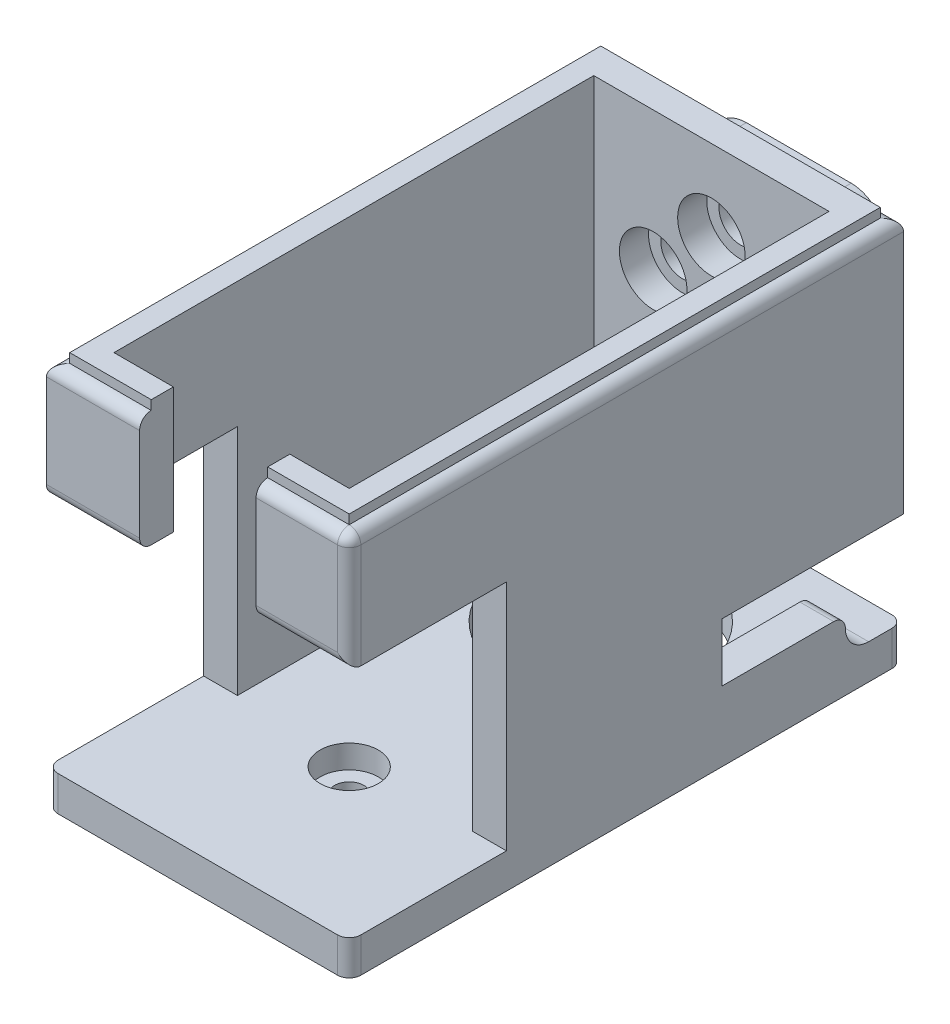
SolidWorks part; units mm, degrees
other "Markup1"
sketch "Sketch34" plane through (-13, 10, 23.5) normal (-0.1734, 0.635, 0.7528) x (0.9767, 0.2093, 0.0485)
ref_plane "Front Plane" through (0, 0, 0) normal (0, 0, 1) x (1, 0, 0)
ref_plane "Top Plane" through (0, 0, 0) normal (0, 1, 0) x (1, 0, 0)
ref_plane "Right Plane" through (0, 0, 0) normal (1, 0, 0) x (0, 0, -1)
sketch "Sketch1" plane through (0, 0, 0) normal (0, 1, 0) x (1, 0, 0)
  line L0 (5, -23.5) -> (13, -23.5)
  line L1 (-10, 20.5) -> (10, 20.5)
  line L2 (-10, 20.5) -> (-10, -20.5)
  line L3 (-10, -20.5) -> (-5, -20.5)
  line L4 (10, 20.5) -> (10, -20.5)
  line L5 (-10, 20.5) -> (10, -20.5) construction
  line L6 (-10, -20.5) -> (10, 20.5) construction
  line L7 (-13, 23.5) -> (13, 23.5)
  line L8 (-13, 23.5) -> (-13, -23.5)
  line L9 (-13, -23.5) -> (-5, -23.5)
  line L10 (13, 23.5) -> (13, -23.5)
  line L11 (-13, 23.5) -> (13, -23.5) construction
  line L12 (-13, -23.5) -> (13, 23.5) construction
  line L14 (-5, -20.5) -> (-5, -23.5)
  line L16 (5, -20.5) -> (5, -23.5)
  line L17 (5, -20.5) -> (10, -20.5)
  point P0 (0, 0)
  point P6 (0, 0)
  dimension "D1" = 20
  dimension "D2" = 41
  dimension "D3" = 3
  dimension "D4" = 3
  dimension "D5" = 5
  dimension "D6" = 5
extrude "Boss-Extrude1" add sketch "Sketch1" along normal blind 10
sketch "Sketch2" plane through (13, 0, 0) normal (1, 0, 0) x (0, 0, -1)
  line L0 (-23.5, 0) -> (23.5, 0) construction
  line L1 (-10, 0) -> (10, 0)
  line L2 (-10, 0) -> (-10, -17)
  line L3 (-10, -17) -> (10, -17)
  line L4 (10, 0) -> (10, -17)
  dimension "D1" = 10
  dimension "D2" = 10
  dimension "D3" = 17
extrude "Boss-Extrude2" add sketch "Sketch2" against normal blind 3
ref_plane "Plane1" through (0, 0, 0) normal (1, 0, 0) x (0, 0, -1)
mirror "Mirror1" about plane through (0, 0, 0) normal (1, 0, 0) of "Boss-Extrude2"
sketch "Sketch3" plane through (0, -17, 0) normal (0, -1, 0) x (1, 0, 0)
  line L1 (-13, 23.5) -> (13, 23.5)
  line L2 (-13, 23.5) -> (-13, -23.5)
  line L3 (-13, -23.5) -> (13, -23.5)
  line L4 (13, 23.5) -> (13, -23.5)
extrude "Boss-Extrude3" add sketch "Sketch3" along normal blind 3
sketch "Sketch5" plane through (0, -20, 0) normal (0, -1, 0) x (1, 0, 0)
  line L1 (10, 20.5) -> (5, 20.5) construction
  line L2 (10, 10) -> (10, -10) construction
  line L3 (-10, 10) -> (-10, -10) construction
  line L4 (-8, -4.5) -> (8, -4.5)
  line L5 (-8, -4.5) -> (-8, -8.5)
  line L6 (-8, -8.5) -> (8, -8.5)
  line L7 (8, -4.5) -> (8, -8.5)
  line L8 (-8, -12.5) -> (8, -12.5)
  line L9 (-8, -12.5) -> (-8, -16.5)
  line L10 (-8, -16.5) -> (8, -16.5)
  line L11 (8, -12.5) -> (8, -16.5)
  line L12 (-10, -10) -> (-10, -20.5) construction
  line L13 (10, -20.5) -> (10, -10) construction
  line L14 (-10, -20.5) -> (10, -20.5) construction
  circle A0 centre (0, 10.5) radius 8
  dimension "D1" = 10
  dimension "D2" = 10
  dimension "D3" = 2
  dimension "D4" = 2
  dimension "D5" = 2
  dimension "D6" = 2
  dimension "D7" = 4
  dimension "D8" = 4
  dimension "D9" = 4
  dimension "D10" = 4
extrude "Cut-Extrude1" cut sketch "Sketch5" against normal through all
sketch "Sketch6" plane through (13, 0, 0) normal (1, 0, 0) x (0, 0, -1)
  line L0 (23.5, -20) -> (23.5, 20.7) construction
  line L1 (23.5, -20) -> (-23.5422, -20) construction
  line L2 (23.5, -20) -> (23.5, 20.7) construction
  line L3 (23.5, 20.7) -> (-23.5422, 20.7) construction
  line L4 (-23.5422, -20) -> (-23.5422, 20.7) construction
  line L5 (23.5, -20) -> (23.5, 20.7) construction
  line L6 (23.5, 0.35) -> (-23.5422, 0.35) construction
  line L7 (10, -17) -> (10, 0) construction
  line L8 (23.5, 4.35) -> (29.5, 4.35)
  line L9 (23.5, 4.35) -> (23.5, -3.65)
  line L10 (23.5, -3.65) -> (29.5, -3.65)
  line L11 (29.5, 4.35) -> (29.5, -3.65)
  line L12 (23.5, 0) -> (10, 0)
  line L13 (23.5, 0) -> (23.5, -9.3)
  line L14 (23.5, -9.3) -> (10, -9.3)
  line L15 (10, 0) -> (10, -9.3)
  line M19 (10, -17) -> (10, 0)
  line M20 (10, 0) -> (23.5, 0)
  line M21 (23.5, 0) -> (23.5, 10)
  dimension "D1" = 40.7
  dimension "D2" = 4
  dimension "D3" = 4
  dimension "D4" = 6
  dimension "D5" = 5.65
extrude "Boss-Extrude4" add sketch "Sketch6" against normal blind 26 contours L11 L8 L9 L10 M21 | L14 L13 L9 M20 M19 region at (13, 0.35, -26.5) region at (13, -4.65, -16.75)
sketch "Sketch7" plane through (0, 0, 0) normal (0, 1, 0) x (1, 0, 0)
  line L1 (-10, 20.5) -> (10, 20.5)
  line L2 (-10, 20.5) -> (-10, 10)
  line L3 (-10, 10) -> (10, 10)
  line L4 (10, 20.5) -> (10, 10)
extrude "Cut-Extrude2" cut sketch "Sketch7" against normal blind 10
sketch "Sketch9" plane through (0, 4.35, 0) normal (0, 1, 0) x (1, 0, 0)
  line L0 (13, 23.5) -> (-13, 23.5) construction
  line L1 (-13, 29.5) -> (-5, 29.5)
  line L2 (-13, 29.5) -> (-13, 23.5)
  line L3 (-13, 23.5) -> (-5, 23.5)
  line L4 (-5, 29.5) -> (-5, 23.5)
  line L5 (-13, 23.5) -> (13, 23.5) construction
  line L6 (13, 29.5) -> (5, 29.5)
  line L7 (13, 29.5) -> (13, 23.5)
  line L8 (13, 23.5) -> (5, 23.5)
  line L9 (5, 29.5) -> (5, 23.5)
  dimension "D1" = 8
  dimension "D2" = 8
extrude "Cut-Extrude3" cut sketch "Sketch9" against normal blind 10
sketch "Sketch10" plane through (0, 0, -29.5) normal (0, 0, -1) x (-1, 0, 0)
  line L1 (-15, 15) -> (15, 15)
  line L2 (-15, 15) -> (-15, -15)
  line L3 (-15, -15) -> (15, -15)
  line L4 (15, 15) -> (15, -15)
  line L5 (-15, 15) -> (15, -15) construction
  line L6 (-15, -15) -> (15, 15) construction
  point P0 (0, 0)
  dimension "D1" = 30
  dimension "D2" = 30
extrude "Boss-Extrude5" add sketch "Sketch10" along normal blind 3
sketch "Sketch11" plane through (0, 0, -32.5) normal (0, 0, -1) x (-1, 0, 0)
  circle A0 centre (0, 10) radius 1.75
  circle A4 centre (10, 0) radius 1.75
  circle A5 centre (0, -10) radius 1.75
  circle A6 centre (-10, 0) radius 1.75
  point P12 (-1, 1)
  point P13 (0, 0)
  dimension "D1" = 3.5
  dimension "D3" = 0
  dimension "D4" = 4
  dimension "D5" = 10
  dimension "D6" = 10
  dimension "D2" = 10
extrude "Cut-Extrude4" cut sketch "Sketch11" against normal blind 5
sketch "Sketch12" plane through (0, -20, 0) normal (0, -1, 0) x (1, 0, 0)
  line L9 (-13, 23.5) -> (13, 23.5)
  line L10 (-13, 23.5) -> (-13, -23.5)
  line L11 (-13, -23.5) -> (13, -23.5)
  line L12 (13, 23.5) -> (13, -23.5)
  circle A0 centre (0, 10.5) radius 8
extrude "Boss-Extrude6" add sketch "Sketch12" along normal blind 3
sketch "Sketch14" plane through (0, -17, 0) normal (0, 1, 0) x (1, 0, 0)
  line L1 (-13, 23.5) -> (13, 23.5)
  line L2 (-13, 23.5) -> (-13, -23.5)
  line L3 (-13, -23.5) -> (13, -23.5)
  line L4 (13, 23.5) -> (13, -23.5)
  line L5 (-13, 10) -> (-10, 10)
  line L6 (-13, 10) -> (-13, -10)
  line L7 (-13, -10) -> (-10, -10)
  line L8 (-10, 10) -> (-10, -10)
  line L9 (10, -10) -> (13, -10)
  line L10 (10, -10) -> (10, 10)
  line L11 (10, 10) -> (13, 10)
  line L12 (13, -10) -> (13, 10)
  circle M1 centre (0, -10.5) radius 8
  line M2 (8, 4.5) -> (-8, 4.5)
  line M3 (-8, 4.5) -> (-8, 8.5)
  line M4 (-8, 8.5) -> (8, 8.5)
  line M5 (8, 8.5) -> (8, 4.5)
  line M6 (8, 12.5) -> (-8, 12.5)
  line M7 (-8, 12.5) -> (-8, 16.5)
  line M8 (-8, 16.5) -> (8, 16.5)
  line M9 (8, 16.5) -> (8, 12.5)
  line M10 (13, -10) -> (10, -10)
  line M11 (10, -10) -> (10, 10)
  line M12 (10, 10) -> (13, 10)
  line M13 (13, 10) -> (13, 23.5)
  line M14 (13, 23.5) -> (-13, 23.5)
  line M15 (-13, 23.5) -> (-13, 10)
  line M16 (-13, 10) -> (-10, 10)
  line M17 (-10, 10) -> (-10, -10)
  line M18 (-10, -10) -> (-13, -10)
  line M19 (-13, -10) -> (-13, -23.5)
  line M20 (-13, -23.5) -> (13, -23.5)
  line M21 (13, -23.5) -> (13, -10)
extrude "Cut-Extrude5" cut sketch "Sketch14" against normal blind 3 contours M21 M10 M11 M12 M13 M14 M15 M16 M17 M18 M19 M20 M5 M2 M3 M4 M9 M6 M7 M8 M1 region at (0, -17, -0.9925)
sketch "Sketch15" plane through (13, 0, 0) normal (1, 0, 0) x (0, 0, -1)
  line L0 (10, -20) -> (23.5, -20) construction
  line L1 (23.5, -17) -> (-23.5, -17)
  line L2 (23.5, -17) -> (23.5, 20.7)
  line L3 (23.5, 20.7) -> (-23.5, 20.7)
  line L4 (-23.5, -17) -> (-23.5, 20.7)
  line L5 (23.5, -23) -> (-23.5, -23) construction
  line L6 (11.2985, 20.7) -> (11.2985, -23) construction
  line L7 (11.2985, -23) -> (11.2985, -1.15) construction
  line L8 (11.2985, -1.15) -> (42.746, -1.15) construction
  line L10 (32.5, 15) -> (23.5, 15)
  line L11 (32.5, 15) -> (32.5, -15.2438)
  line L12 (32.5, -15.2438) -> (23.5, -15.2438)
  line L13 (23.5, 15) -> (23.5, -15.2438)
  line M11 (23.5, -9.3) -> (23.5, 10)
  dimension "D1" = 3
  dimension "D2" = 43.7
extrude "Cut-Extrude7" cut sketch "Sketch15" against normal through all both and the other way through all contours L12 L11 L10 L2 M11 region at (13, -0.1219, -28)
sketch "Sketch16" plane through (0, -9.3, 0) normal (0, -1, 0) x (1, 0, 0)
  line L0 (-13, 23.5) -> (-13, -23.5) construction
  line L1 (13, -23.5) -> (-13, -23.5)
  line L2 (13, -23.5) -> (13, -10)
  line L3 (13, -10) -> (-13, -10)
  line L4 (-13, -23.5) -> (-13, -10)
  line L5 (10, -10) -> (13, -10) construction
  line L7 (10, -20.5) -> (-10, -20.5)
  line L8 (10, -20.5) -> (10, -10)
  line L9 (10, -10) -> (-10, -10)
  line L10 (-10, -20.5) -> (-10, -10)
  line M2 (10, -20.5) -> (-10, -20.5)
  line M3 (-10, -20.5) -> (-10, -10)
  line M4 (-10, -10) -> (-13, -10)
  line M5 (-13, -10) -> (-13, -23.5)
  line M6 (-13, -23.5) -> (13, -23.5)
  line M7 (13, -23.5) -> (13, -10)
  line M8 (13, -10) -> (10, -10)
  line M9 (10, -10) -> (10, -20.5)
  dimension "D1" = 0
extrude "Boss-Extrude7" add sketch "Sketch16" along normal blind 10.7 contours M9 M2 M3 M4 M5 M6 M7 M8 region at (0, -9.3, -23.207)
sketch "Sketch18" plane through (13, 0, 0) normal (1, 0, 0) x (0, 0, -1)
  line L0 (23.5, 10) -> (23.5, -23) construction
  line L1 (23.5, -17) -> (8.5, -17)
  line L2 (23.5, -17) -> (23.5, -12)
  line L3 (23.5, -12) -> (8.5, -12)
  line L4 (8.5, -17) -> (8.5, -12)
  line L5 (-23.5, -20) -> (-10, -20) construction
  dimension "D1" = 3
  dimension "D2" = 15
  dimension "D3" = 5
extrude "Cut-Extrude8" cut sketch "Sketch18" against normal blind 10
mirror "Mirror2" about plane through (0, 0, 0) normal (1, 0, 0) of "Cut-Extrude8"
sketch "Sketch21" plane through (0, 0, -23.5) normal (0, 0, -1) x (-1, 0, 0)
  line L0 (0, 20.7) -> (0, -23) construction
  line L1 (-13, -23) -> (13, -23)
  line L2 (-13, -23) -> (-13, 20.7)
  line L3 (-13, 20.7) -> (13, 20.7)
  line L4 (13, -23) -> (13, 20.7)
  line L5 (0, -23) -> (0, -1.15) construction
  line L6 (0, -1.15) -> (13, -1.15) construction
  circle A0 centre (0, 3.85) radius 1.85
  circle A1 centre (5, -1.15) radius 1.85
  circle A2 centre (0, -6.15) radius 1.85
  circle A3 centre (-5, -1.15) radius 1.85
  point P19 (0, -1.15)
  dimension "D2" = 5
  dimension "D3" = 3.7
  dimension "D5" = 5
  dimension "D6" = 5
  dimension "D1" = 43.7
  dimension "D4" = 4
extrude "Cut-Extrude9" cut sketch "Sketch21" against normal blind 5 contours A3 | A0 | A1 | A2 region at (0, 3.85, -23.5) region at (-5, -1.15, -23.5) region at (0, -6.15, -23.5) region at (5, -1.15, -23.5)
sketch "Sketch22" plane through (0, 0, -20.5) normal (0, 0, 1) x (1, 0, 0)
  line L0 (0, 3.85) -> (0, -6.15) construction
  line L1 (0, -6.15) -> (0, -1.15) construction
  line L2 (0, -1.15) -> (5, -1.15) construction
  circle A0 centre (0, 3.85) radius 2.9
  circle A1 centre (5, -1.15) radius 2.9
  circle A2 centre (0, -6.15) radius 2.9
  circle A3 centre (-5, -1.15) radius 2.9
  point P17 (0, -1.15)
  dimension "D1" = 5.8
  dimension "D2" = 4
extrude "Cut-Extrude10" cut sketch "Sketch22" against normal blind 2.6
sketch "Sketch23" plane through (0, 0, -23.5) normal (0, 0, -1) x (-1, 0, 0)
  line L0 (-3, -17) -> (-13, -17)
  line L1 (-13, 10) -> (13, 10)
  line L2 (-13, 10) -> (-13, -12)
  line L3 (-13, -12) -> (-3, -12)
  line L4 (13, 10) -> (13, -12)
  line L10 (-3, -12) -> (-3, -17)
  line L12 (3, -12) -> (3, -17)
  line L13 (13, -17) -> (3, -17)
  line L14 (13, -17) -> (13, -23)
  line L15 (13, -23) -> (-13, -23)
  line L16 (-13, -17) -> (-13, -23)
  line L17 (3, -12) -> (13, -12)
  circle A0 centre (0, 3.85) radius 1.75
  circle A1 centre (0, -6.15) radius 1.75
  circle A2 centre (5, -1.15) radius 1.75
  circle A3 centre (-5, -1.15) radius 1.75
  circle M1 centre (-5, -1.15) radius 1.85
  circle M2 centre (0, 3.85) radius 1.85
  circle M3 centre (5, -1.15) radius 1.85
  circle M4 centre (0, -6.15) radius 1.85
  line M5 (3, -12) -> (13, -12)
  line M6 (13, -12) -> (13, 10)
  line M7 (13, 10) -> (-13, 10)
  line M8 (-13, 10) -> (-13, -12)
  line M9 (-13, -12) -> (-3, -12)
extrude "Boss-Extrude11" add sketch "Sketch23" along normal blind 0.6 contours L3 M9 M5 M6 M7 M8 M2 M4 M3 M1 region at (2.5799, -14.5, -23.5)
sketch "Sketch24" plane through (0, 0, -24.1) normal (0, 0, -1) x (-1, 0, 0)
  line L5 (5, -1.15) -> (0, -1.15) construction
  line L7 (0, 3.85) -> (0, -6.15) construction
  line L8 (-4.5, 6.35) -> (4.5, 6.35)
  line L9 (-13, 6.35) -> (-13, -8.65)
  line L10 (-4.5, -8.65) -> (4.5, -8.65)
  line L11 (13, 6.35) -> (13, -8.65)
  line L12 (-13, 6.35) -> (13, -8.65) construction
  line L13 (-13, -8.65) -> (13, 6.35) construction
  line L15 (-7.5, 6.35) -> (7.5, 6.35)
  line L16 (-7.5, 3.35) -> (-7.5, -5.65)
  line L17 (-7.5, -8.65) -> (7.5, -8.65)
  line L18 (7.5, 3.35) -> (7.5, -5.65)
  line L19 (-7.5, 6.35) -> (7.5, -8.65) construction
  line L20 (-7.5, -8.65) -> (7.5, 6.35) construction
  circle A0 centre (0, 3.85) radius 1.75
  circle A1 centre (0, -6.15) radius 1.75
  circle A2 centre (5, -1.15) radius 1.75
  circle A3 centre (-5, -1.15) radius 1.75
  arc A4 (7.5, 3.35) -> (4.5, 6.35) centre (4.5, 3.35) ccw
  arc A5 (7.5, -5.65) -> (4.5, -8.65) centre (4.5, -5.65) cw
  arc A6 (-4.5, -8.65) -> (-7.5, -5.65) centre (-4.5, -5.65) cw
  arc A7 (-7.5, 3.35) -> (-4.5, 6.35) centre (-4.5, 3.35) cw
  point P0 (0, -0.7463)
  circle M11 centre (0, 3.85) radius 1.85
  circle M12 centre (0, -6.15) radius 1.85
  circle M25 centre (5, -1.15) radius 1.85
  circle M26 centre (-5, -1.15) radius 1.85
  dimension "D3" = 3
  dimension "D2" = 15
extrude "Boss-Extrude12" add sketch "Sketch24" along normal blind 4 contours A7 L16 A6 L10 A5 L18 A4 L8 M12 M25 M26 M11 region at (0, -1.15, -24.1)
sketch "Sketch25" plane through (0, 0, -24.1) normal (0, 0, -1) x (-1, 0, 0)
  line L1 (-10, -17) -> (-3, -17)
  line L2 (-10, -17) -> (-10, -20)
  line L3 (-10, -20) -> (-3, -20)
  line L4 (-3, -17) -> (-3, -20)
  line L5 (3, -17) -> (10, -17)
  line L6 (3, -17) -> (3, -20)
  line L7 (3, -20) -> (10, -20)
  line L8 (10, -17) -> (10, -20)
  dimension "D1" = 3
  dimension "D2" = 3
extrude "Cut-Extrude11" cut sketch "Sketch25" against normal blind 5
sketch "Sketch26" plane through (0, 10, 0) normal (0, 1, 0) x (1, 0, 0)
  line L0 (-10, 20.5) -> (10, 20.5) construction
  line L1 (-10.1, 20.6) -> (10.1, 20.6)
  line L2 (-10.1, 20.6) -> (-10.1, -20.6)
  line L3 (-10.1, -20.6) -> (10.1, -20.6)
  line L4 (10.1, 20.6) -> (10.1, -20.6)
  line L5 (-10, -20.5) -> (-10, 20.5) construction
  line L6 (10, -10) -> (10, 24.1) construction
  line L7 (-5, -20.5) -> (-10, -20.5) construction
  dimension "D1" = 0.1
  dimension "D2" = 0.1
  dimension "D3" = 0.1
  dimension "D4" = 0.1
extrude "Cut-Extrude12" cut sketch "Sketch26" against normal blind 30
sketch "Sketch27" plane through (0, 0, -24.1) normal (0, 0, -1) x (-1, 0, 0)
  line L0 (0, -23) -> (0, -16.7281) construction
  line L1 (-13, -23) -> (13, -23) construction
  line L2 (-10, -20) -> (-10.1, -20)
  line L3 (10, -17) -> (10.1, -17)
  line L4 (10, -17) -> (10, -20)
  line L5 (10, -20) -> (10.1, -20)
  line L6 (10.1, -17) -> (10.1, -20)
  line L7 (-10.1, -17) -> (-10.1, -20)
  line L8 (-10, -17) -> (-10.1, -17)
  line L9 (-10, -17) -> (-10, -20)
extrude "Cut-Extrude13" cut sketch "Sketch27" against normal through all
sketch "Sketch28" plane through (0, -23, 0) normal (0, -1, 0) x (1, 0, 0)
  line L0 (0, 10.5) -> (0, 23.5) construction
  line L1 (13, 23.5) -> (-13, 23.5) construction
  line L2 (0, -24.1) -> (0, -11.1) construction
  line L3 (4.5, -24.1) -> (-4.5, -24.1) construction
  line L4 (0, 10.5) -> (0, -11.1) construction
  circle A0 centre (0, -11.1) radius 8
  dimension "D2" = 16
  dimension "D1" = 13
extrude "Cut-Extrude14" cut sketch "Sketch28" against normal through all
sketch "Sketch29" plane through (0, 0, -24.1) normal (0, 0, -1) x (-1, 0, 0)
  line L0 (-13, -17) -> (-13, -23) construction
  line L1 (-10.1, -17) -> (-13, -17)
  line L2 (-10.1, -17) -> (-10.1, -20)
  line L3 (-10.1, -20) -> (-13, -20)
  line L4 (-13, -17) -> (-13, -20)
  line L6 (10.1, -20) -> (13, -20)
  line L7 (10.1, -20) -> (10.1, -17)
  line L8 (10.1, -17) -> (13, -17)
  line L9 (13, -20) -> (13, -17)
extrude "Cut-Extrude15" cut sketch "Sketch29" against normal blind 5
fillet "Fillet1" radius 2 2 edges at (-3, -20, -22.35) (3, -20, -22.35)
fillet "Fillet2" radius 2 2 edges at (-11.55, -20, -19.1) (11.55, -20, -19.1)
fillet "Fillet3" radius 1 14 edges at (-11.55, -17, -19.1) (11.55, -17, -19.1) (-13, -21.5, -24.1) (13, -21.5, -24.1) (-13, -21.5, 23.5) (13, -21.5, 23.5) (0, 10, -24.1) (-13, 10, -0.3) (-9, 0, 23.5) (-9, 10, 23.5) (9, 0, 23.5) (9, 10, 23.5) (13, 10, -0.3) (13, 5, 23.5)
sketch "Sketch35" plane through (0, -20, 0) normal (0, 1, 0) x (1, 0, 0)
  circle A0 centre (0, -10.5) radius 8
  circle A1 centre (0, -10.5) radius 2.5
  dimension "D1" = 5
extrude "Boss-Extrude13" add sketch "Sketch35" against normal blind 5
sketch "Sketch36" plane through (0, 10, 0) normal (0, 1, 0) x (1, 0, 0)
  line L1 (-12, 23.1) -> (12, 23.1)
  line L2 (-12, 23.1) -> (-12, -22.5)
  line L3 (-12, -22.5) -> (12, -22.5)
  line L4 (12, 23.1) -> (12, -22.5)
  line L5 (10.1, -20.6) -> (-10.1, -20.6)
  line L6 (10.1, -20.6) -> (10.1, 20.6)
  line L7 (10.1, 20.6) -> (-10.1, 20.6)
  line L8 (-10.1, -20.6) -> (-10.1, 20.6)
  line L9 (-5, -22.5) -> (5, -22.5)
  line L10 (-5, -22.5) -> (-5, -20.6)
  line L11 (-5, -20.6) -> (5, -20.6)
  line L12 (5, -22.5) -> (5, -20.6)
  line M1 (-12, 23.1) -> (-12, -22.5)
  line M2 (-12, -22.5) -> (-5, -22.5)
  line M3 (-5, -22.5) -> (-5, -20.6)
  line M4 (-5, -20.6) -> (-10.1, -20.6)
  line M5 (-10.1, -20.6) -> (-10.1, 20.6)
  line M6 (-10.1, 20.6) -> (10.1, 20.6)
  line M7 (10.1, 20.6) -> (10.1, -20.6)
  line M8 (10.1, -20.6) -> (5, -20.6)
  line M9 (5, -20.6) -> (5, -22.5)
  line M10 (5, -22.5) -> (12, -22.5)
  line M11 (12, -22.5) -> (12, 23.1)
  line M12 (12, 23.1) -> (-12, 23.1)
extrude "Boss-Extrude14" add sketch "Sketch36" along normal blind 0.8 contours M12 M1 M2 M3 M4 M5 M6 M7 M8 M9 M10 M11 region at (0, 10, -22.5847)
sketch "Sketch38" plane through (0, -25, 0) normal (0, -1, 0) x (1, 0, 0)
  circle A0 centre (0, 10.5) radius 2.5
  circle A1 centre (0, 10.5) radius 2.55
  dimension "D1" = 5.1
extrude "Cut-Extrude16" cut sketch "Sketch38" against normal blind 2
sketch "Sketch39" plane through (0, -23, 0) normal (0, -1, 0) x (1, 0, 0)
  circle A0 centre (0, 10.5) radius 2.55
  circle A1 centre (0, 10.5) radius 1.25
  dimension "D1" = 2.5
extrude "Boss-Extrude15" add sketch "Sketch39" against normal blind 1
sketch "Sketch40" plane through (0, -25, 0) normal (0, -1, 0) x (1, 0, 0)
  circle A0 centre (0, 10.5) radius 8
  circle A1 centre (0, 10.5) radius 6.5
  dimension "D1" = 13
  dimension "D2" = 16
extrude "Cut-Extrude17" cut sketch "Sketch40" against normal blind 4
